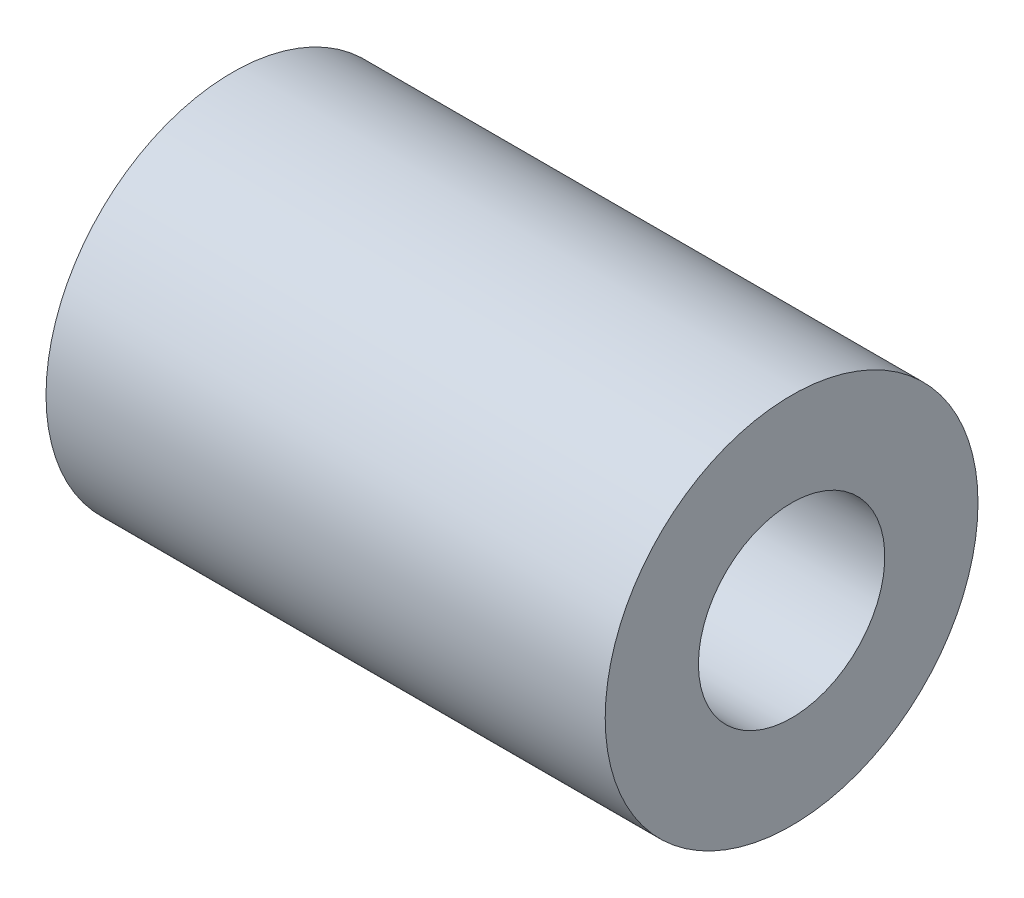
SolidWorks part; units mm, degrees
ref_plane "Top" through (0, 0, 0) normal (0, 0, 1) x (1, 0, 0)
ref_plane "Front" through (0, 0, 0) normal (0, 1, 0) x (1, 0, 0)
ref_plane "Right" through (0, 0, 0) normal (1, 0, 0) x (0, 0, -1)
sketch "Sketch1" plane through (0, 0, 0) normal (1, 0, 0) x (0, 0, -1)
  circle A0 centre (0, 0) radius 1.5875
  circle A1 centre (0, 0) radius 3.175
  dimension "D1" = 3.175
  dimension "D2" = 6.35
extrude "Extrude1" add sketch "Sketch1" along normal mid plane 9.525
ref_axis "Axis1" through (5.7843, 0, 0) along (-1, 0, 0)
